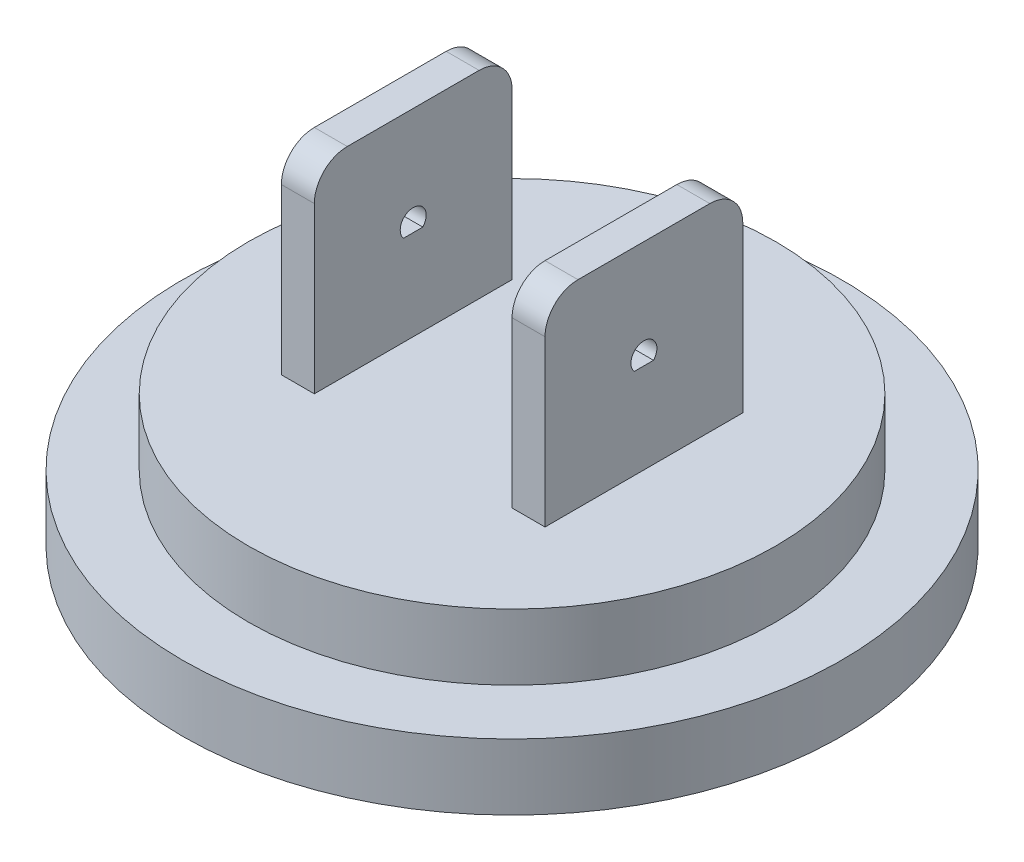
SolidWorks part; units mm, degrees
ref_plane "Front Plane" through (0, 0, 0) normal (0, 0, 1) x (1, 0, 0)
ref_plane "Top Plane" through (0, 0, 0) normal (0, 1, 0) x (1, 0, 0)
ref_plane "Right Plane" through (0, 0, 0) normal (1, 0, 0) x (0, 0, -1)
sketch "Sketch2" plane through (0, 0, 0) normal (0, 1, 0) x (1, 0, 0)
  circle A1 centre (0, 0) radius 63.5
  dimension "D2" = 127
extrude "Boss-Extrude1" add sketch "Sketch2" along normal blind 12.7
sketch "Sketch3" plane through (0, 12.7, 0) normal (0, 1, 0) x (1, 0, 0)
  circle A0 centre (0, 0) radius 50.8
  dimension "D1" = 101.6
extrude "Boss-Extrude2" add sketch "Sketch3" along normal blind 12.7
sketch "Sketch4" plane through (0, 0, 0) normal (0, -1, 0) x (1, 0, 0)
  circle A0 centre (0, 0) radius 6.35
  dimension "D1" = 12.7
extrude "Boss-Extrude3" add sketch "Sketch4" along normal blind 25.4
sketch "Sketch5" plane through (0, 25.4, 0) normal (0, 1, 0) x (1, 0, 0)
  line L0 (0, 0) -> (0, 17.7689) construction
  line L1 (25.4, -19.05) -> (19.05, -19.05)
  line L2 (-25.4, 19.05) -> (-19.05, 19.05)
  line L3 (-25.4, 19.05) -> (-25.4, -19.05)
  line L4 (-25.4, -19.05) -> (-19.05, -19.05)
  line L5 (-19.05, 19.05) -> (-19.05, -19.05)
  line L6 (19.05, 19.05) -> (19.05, -19.05)
  line L7 (25.4, 19.05) -> (19.05, 19.05)
  line L8 (25.4, 19.05) -> (25.4, -19.05)
  dimension "D1" = 6.35
  dimension "D2" = 38.1
  dimension "D3" = 19.05
  dimension "D4" = 19.05
extrude "Boss-Extrude4" add sketch "Sketch5" along normal blind 38.1
fillet "Fillet1" radius 6.35 4 edges at (22.225, 63.5, 19.05) (-22.225, 63.5, 19.05) (22.225, 63.5, -19.05) (-22.225, 63.5, -19.05)
sketch "Sketch6" plane through (-25.4, 0, 0) normal (-1, 0, 0) x (0, 0, 1)
  line L0 (-12.7, 63.5) -> (12.7, 63.5) construction
  line L1 (19.05, 57.15) -> (19.05, 25.4) construction
  line L2 (-1.8555, 42.7717) -> (1.8555, 42.7717)
  arc A0 (1.8555, 42.7717) -> (-1.8555, 42.7717) centre (0, 44.45) ccw
  point P8 (0, 0)
  point P9 (0, 0)
  point P10 (0, 0)
  dimension "D1" = 5.0038
  dimension "D2" = 19.05
  dimension "D3" = 19.05
  dimension "D4" = 3.711
extrude "Cut-Extrude1" cut sketch "Sketch6" against normal through all
sketch "Sketch7" plane through (0, -25.4, 0) normal (0, -1, 0) x (1, 0, 0)
  line L8 (0, 5.08) -> (0.7102, 6.3102)
  line L9 (0, 5.08) -> (-0.7102, 6.3102)
  arc A6 (0.7102, 6.3102) -> (-0.7102, 6.3102) centre (0, 0) ccw
extrude "Cut-Extrude2" cut sketch "Sketch7" against normal blind 12.7
pattern_circular "CirPattern1" count 28 over 360 about axis through (0, -25.4, 0) along (0, 1, 0) of "Cut-Extrude2" reverse direction yes
